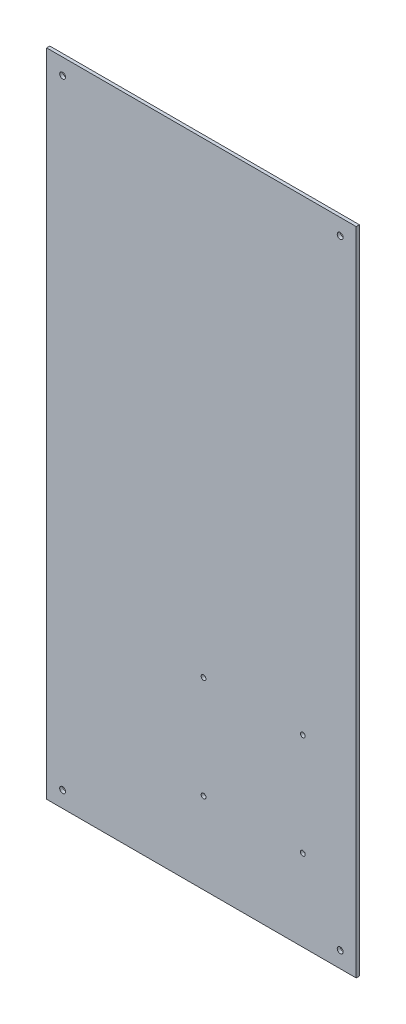
SolidWorks part; units mm, degrees
material "Acrylic (Medium-high impact)"
ref_plane "Front Plane" through (0, 0, 0) normal (0, 0, 1) x (1, 0, 0)
ref_plane "Top Plane" through (0, 0, 0) normal (0, 1, 0) x (1, 0, 0)
ref_plane "Right Plane" through (0, 0, 0) normal (1, 0, 0) x (0, 0, -1)
sketch "Sketch1" plane through (0, 0, 0) normal (0, 0, 1) x (1, 0, 0)
  line L0 (159.5, 0) -> (-159.5, 0) construction
  line L1 (-145, 304.8) -> (145, 304.8)
  line L2 (-145, 304.8) -> (-145, -304.8)
  line L3 (-145, -304.8) -> (145, -304.8)
  line L4 (145, 304.8) -> (145, -304.8)
  line L5 (-145, 304.8) -> (145, -304.8) construction
  line L6 (-145, -304.8) -> (145, 304.8) construction
  point P0 (0, 0)
  point P5 (-129.995, 289.795)
  point P6 (129.995, 289.795)
  point P7 (2, -228.6)
  point P9 (2, -132.6)
  point P10 (95, -132.6)
  point P11 (95, -228.6)
  point P12 (0, 0)
  point P13 (0, 0)
  point P16 (129.995, -289.795)
  point P17 (-129.995, -289.795)
  point P18 (0, 0)
  point P19 (0, 0)
  dimension "D1" = 609.6
  dimension "D2" = 290
  dimension "D3" = 15.005
  dimension "D4" = 15.005
  dimension "D5" = 15.005
  dimension "D6" = 96
  dimension "D7" = 93
  dimension "D8" = 76.2
  dimension "D9" = 50
extrude "Boss-Extrude1" add sketch "Sketch1" along normal blind 3
hole_wizard "M5 Clearance Hole1" positions "Sketch2" profile "Sketch3" hole size "M5" standard "ANSI Metric" end condition through all
sketch "Sketch2" plane through (0, 0, 3) normal (0, 0, 1) x (1, 0, 0)
  point P0 (129.995, 289.795)
  point P3 (-129.995, 289.795)
  point P6 (-129.995, -289.795)
  point P9 (129.995, -289.795)
sketch "Sketch3" plane through (129.995, 289.795, 3) normal (1, 0, 0) x (0, -1, 0)
  line L0 (0, 0) -> (0, 3)
  line L1 (0, 3) -> (2.75, 3)
  line L2 (2.75, 3) -> (2.75, 0)
  line L5 (2.75, 0) -> (0, 0)
  line L11 (0, -6.35) -> (0, 107.95) construction
  dimension "Thru Hole Dia." = 5.5
  dimension "Thru Hole Depth" = 3
hole_wizard "M4 Clearance Hole1" positions "Sketch4" profile "Sketch5" hole size "M4" standard "ANSI Metric" end condition up to next
sketch "Sketch4" plane through (0, 0, 3) normal (0, 0, 1) x (1, 0, 0)
  point P0 (95, -132.6)
  point P3 (2, -132.6)
  point P6 (2, -228.6)
  point P9 (95, -228.6)
sketch "Sketch5" plane through (95, -132.6, 3) normal (1, 0, 0) x (0, -1, 0)
  line L0 (0, 0) -> (0, 3)
  line L1 (0, 3) -> (2.25, 3)
  line L2 (2.25, 3) -> (2.25, 0)
  line L5 (2.25, 0) -> (0, 0)
  line L11 (0, -6.35) -> (0, 107.95) construction
  dimension "Thru Hole Dia." = 4.5
  dimension "Thru Hole Depth" = 3
